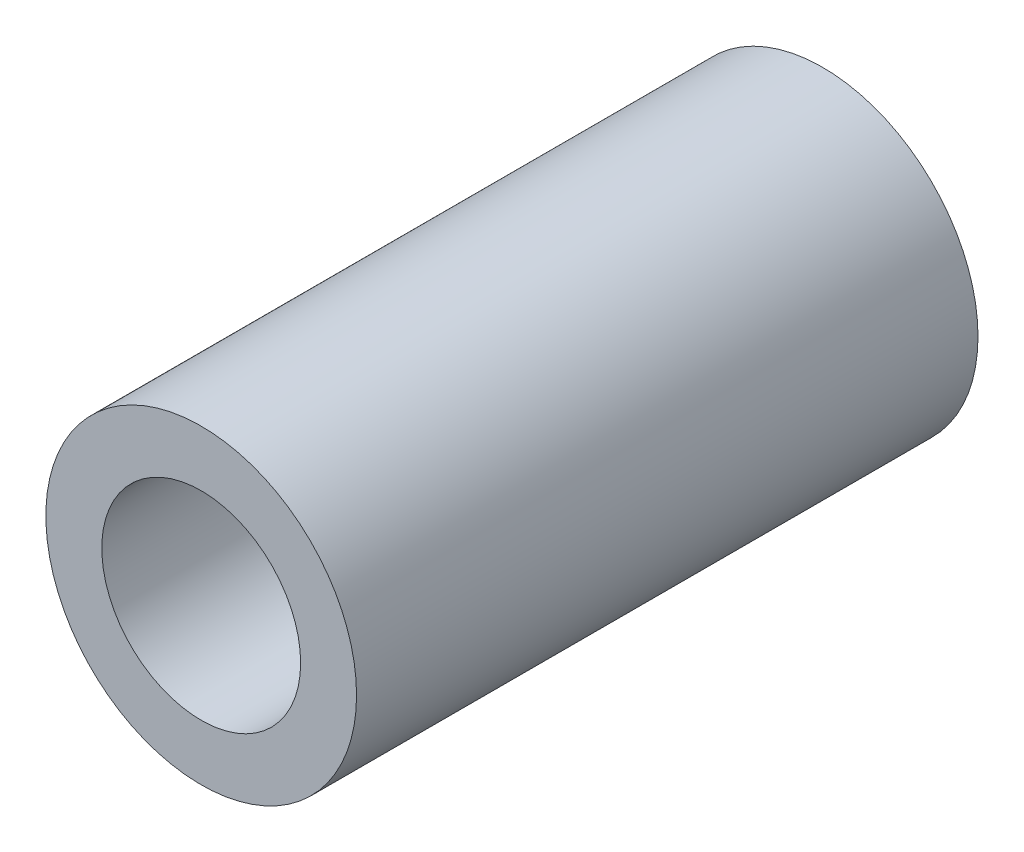
SolidWorks part; units mm, degrees
ref_plane "Front Plane" through (0, 0, 0) normal (0, 0, 1) x (1, 0, 0)
ref_plane "Top Plane" through (0, 0, 0) normal (0, 1, 0) x (1, 0, 0)
ref_plane "Right Plane" through (0, 0, 0) normal (1, 0, 0) x (0, 0, -1)
sketch "Sketch1" plane through (0, 0, 0) normal (0, 0, 1) x (1, 0, 0)
  circle A0 centre (0, 0) radius 2.5
  circle A1 centre (0, 0) radius 1.6
  dimension "D1" = 5
  dimension "D2" = 3.2
extrude "Boss-Extrude1" add sketch "Sketch1" along normal mid plane 10
